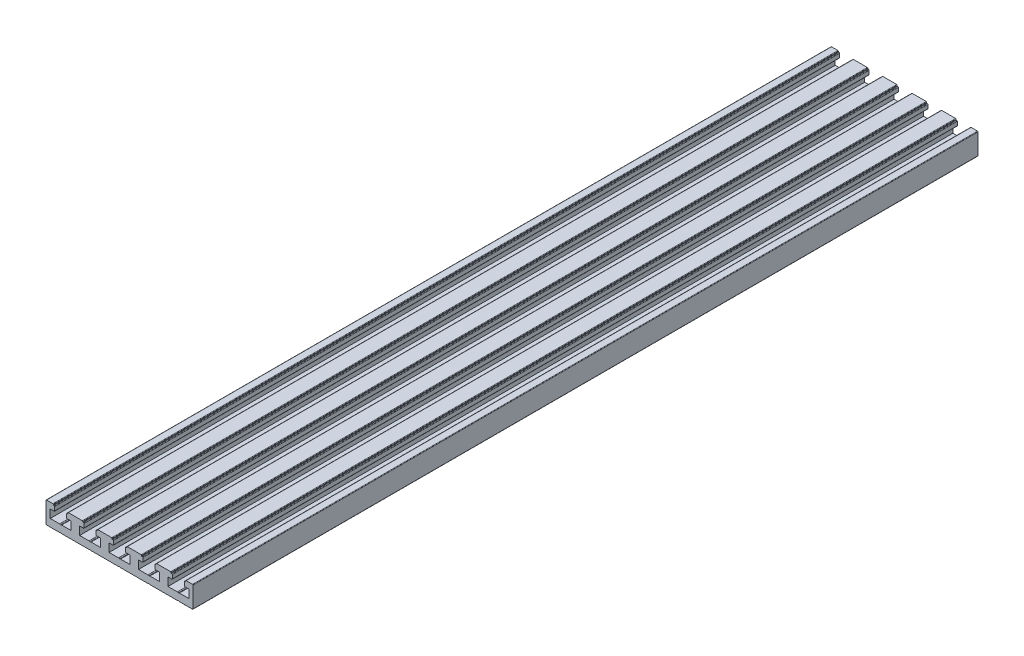
SolidWorks part; units mm, degrees
material "6061-T6 (SS)"
ref_plane "Front Plane" through (0, 0, 0) normal (0, 0, 1) x (1, 0, 0)
ref_plane "Top Plane" through (0, 0, 0) normal (0, 1, 0) x (1, 0, 0)
ref_plane "Right Plane" through (0, 0, 0) normal (1, 0, 0) x (0, 0, -1)
sketch "Sketch1" plane through (0, 0, 0) normal (0, 0, -1) x (-1, 0, 0)
  line L0 (0, 1.72) -> (0, -1.72) construction
  line L1 (-37.45, 8.85) -> (-37.45, -1.65)
  line L2 (-37.2, -1.9) -> (-30.5436, -1.9)
  line L3 (-30.4589, -1.8852) -> (-30, -1.72)
  line L4 (-30, -1.72) -> (-29.5411, -1.8852)
  line L5 (-29.4564, -1.9) -> (-15.5436, -1.9)
  line L6 (-15.4589, -1.8852) -> (-15, -1.72)
  line L7 (-15, -1.72) -> (-14.5411, -1.8852)
  line L8 (-14.4564, -1.9) -> (-0.5436, -1.9)
  line L9 (-0.4589, -1.8852) -> (0, -1.72)
  line L10 (0, -1.72) -> (0.4589, -1.8852)
  line L11 (0.5436, -1.9) -> (14.4564, -1.9)
  line L12 (14.5411, -1.8852) -> (15, -1.72)
  line L13 (15, -1.72) -> (15.4589, -1.8852)
  line L14 (15.5436, -1.9) -> (29.4564, -1.9)
  line L15 (29.5411, -1.8852) -> (30, -1.72)
  line L16 (30, -1.72) -> (30.4589, -1.8852)
  line L17 (30.5436, -1.9) -> (37.2, -1.9)
  line L18 (37.45, -1.65) -> (37.45, 8.85)
  line L19 (37.2, 9.1) -> (33.95, 9.1)
  line L20 (33.7, 8.85) -> (33.7, 8.5)
  line L21 (33.7, 8.5) -> (33.32, 8.5)
  line L22 (33.07, 8.25) -> (33.07, 6.35)
  line L23 (33.32, 6.1) -> (35.3, 6.1)
  line L24 (35.3, 6.1) -> (35.3, 1.9)
  line L25 (35.3, 1.9) -> (30.5436, 1.9)
  line L26 (30.4589, 1.8852) -> (30, 1.72)
  line L27 (30, 1.72) -> (29.5411, 1.8852)
  line L28 (29.4564, 1.9) -> (24.7, 1.9)
  line L29 (24.7, 1.9) -> (24.7, 6.1)
  line L30 (24.7, 6.1) -> (26.68, 6.1)
  line L31 (26.93, 6.35) -> (26.93, 8.25)
  line L32 (26.68, 8.5) -> (26.3, 8.5)
  line L33 (26.3, 8.5) -> (26.3, 8.85)
  line L34 (26.05, 9.1) -> (18.95, 9.1)
  line L35 (18.7, 8.85) -> (18.7, 8.5)
  line L36 (18.7, 8.5) -> (18.32, 8.5)
  line L37 (18.07, 8.25) -> (18.07, 6.35)
  line L38 (18.32, 6.1) -> (20.3, 6.1)
  line L39 (20.3, 6.1) -> (20.3, 1.9)
  line L40 (20.3, 1.9) -> (15.5436, 1.9)
  line L41 (15.4589, 1.8852) -> (15, 1.72)
  line L42 (15, 1.72) -> (14.5411, 1.8852)
  line L43 (14.4564, 1.9) -> (9.7, 1.9)
  line L44 (9.7, 1.9) -> (9.7, 6.1)
  line L45 (9.7, 6.1) -> (11.68, 6.1)
  line L46 (11.93, 6.35) -> (11.93, 8.25)
  line L47 (11.68, 8.5) -> (11.3, 8.5)
  line L48 (11.3, 8.5) -> (11.3, 8.85)
  line L49 (11.05, 9.1) -> (3.95, 9.1)
  line L50 (3.7, 8.85) -> (3.7, 8.5)
  line L51 (3.7, 8.5) -> (3.32, 8.5)
  line L52 (3.07, 8.25) -> (3.07, 6.35)
  line L53 (3.32, 6.1) -> (5.3, 6.1)
  line L54 (5.3, 6.1) -> (5.3, 1.9)
  line L55 (5.3, 1.9) -> (0.5436, 1.9)
  line L56 (0.4589, 1.8852) -> (0, 1.72)
  line L57 (0, 1.72) -> (-0.4589, 1.8852)
  line L58 (-0.5436, 1.9) -> (-5.3, 1.9)
  line L59 (-5.3, 1.9) -> (-5.3, 6.1)
  line L60 (-5.3, 6.1) -> (-3.32, 6.1)
  line L61 (-3.07, 6.35) -> (-3.07, 8.25)
  line L62 (-3.32, 8.5) -> (-3.7, 8.5)
  line L63 (-3.7, 8.5) -> (-3.7, 8.85)
  line L64 (-3.95, 9.1) -> (-11.05, 9.1)
  line L65 (-11.3, 8.85) -> (-11.3, 8.5)
  line L66 (-11.3, 8.5) -> (-11.68, 8.5)
  line L67 (-11.93, 8.25) -> (-11.93, 6.35)
  line L68 (-11.68, 6.1) -> (-9.7, 6.1)
  line L69 (-9.7, 6.1) -> (-9.7, 1.9)
  line L70 (-9.7, 1.9) -> (-14.4564, 1.9)
  line L71 (-14.5411, 1.8852) -> (-15, 1.72)
  line L72 (-15, 1.72) -> (-15.4589, 1.8852)
  line L73 (-15.5436, 1.9) -> (-20.3, 1.9)
  line L74 (-20.3, 1.9) -> (-20.3, 6.1)
  line L75 (-20.3, 6.1) -> (-18.32, 6.1)
  line L76 (-18.07, 6.35) -> (-18.07, 8.25)
  line L77 (-18.32, 8.5) -> (-18.7, 8.5)
  line L78 (-18.7, 8.5) -> (-18.7, 8.85)
  line L79 (-18.95, 9.1) -> (-26.05, 9.1)
  line L80 (-26.3, 8.85) -> (-26.3, 8.5)
  line L81 (-26.3, 8.5) -> (-26.68, 8.5)
  line L82 (-26.93, 8.25) -> (-26.93, 6.35)
  line L83 (-26.68, 6.1) -> (-24.7, 6.1)
  line L84 (-24.7, 6.1) -> (-24.7, 1.9)
  line L85 (-24.7, 1.9) -> (-29.4564, 1.9)
  line L86 (-29.5411, 1.8852) -> (-30, 1.72)
  line L87 (-30, 1.72) -> (-30.4589, 1.8852)
  line L88 (-30.5436, 1.9) -> (-35.3, 1.9)
  line L89 (-35.3, 1.9) -> (-35.3, 6.1)
  line L90 (-35.3, 6.1) -> (-33.32, 6.1)
  line L91 (-33.07, 6.35) -> (-33.07, 8.25)
  line L92 (-33.32, 8.5) -> (-33.7, 8.5)
  line L93 (-33.7, 8.5) -> (-33.7, 8.85)
  line L94 (-33.95, 9.1) -> (-37.2, 9.1)
  arc A0 (-37.45, -1.65) -> (-37.2, -1.9) centre (-37.2, -1.65) ccw
  arc A1 (-30.5436, -1.9) -> (-30.4589, -1.8852) centre (-30.5436, -1.65) ccw
  arc A2 (-29.5411, -1.8852) -> (-29.4564, -1.9) centre (-29.4564, -1.65) ccw
  arc A3 (-15.5436, -1.9) -> (-15.4589, -1.8852) centre (-15.5436, -1.65) ccw
  arc A4 (-14.5411, -1.8852) -> (-14.4564, -1.9) centre (-14.4564, -1.65) ccw
  arc A5 (-0.5436, -1.9) -> (-0.4589, -1.8852) centre (-0.5436, -1.65) ccw
  arc A6 (0.4589, -1.8852) -> (0.5436, -1.9) centre (0.5436, -1.65) ccw
  arc A7 (14.4564, -1.9) -> (14.5411, -1.8852) centre (14.4564, -1.65) ccw
  arc A8 (15.4589, -1.8852) -> (15.5436, -1.9) centre (15.5436, -1.65) ccw
  arc A9 (29.4564, -1.9) -> (29.5411, -1.8852) centre (29.4564, -1.65) ccw
  arc A10 (30.4589, -1.8852) -> (30.5436, -1.9) centre (30.5436, -1.65) ccw
  arc A11 (37.2, -1.9) -> (37.45, -1.65) centre (37.2, -1.65) ccw
  arc A12 (37.45, 8.85) -> (37.2, 9.1) centre (37.2, 8.85) ccw
  arc A13 (33.95, 9.1) -> (33.7, 8.85) centre (33.95, 8.85) ccw
  arc A14 (33.32, 8.5) -> (33.07, 8.25) centre (33.32, 8.25) ccw
  arc A15 (33.07, 6.35) -> (33.32, 6.1) centre (33.32, 6.35) ccw
  arc A16 (30.5436, 1.9) -> (30.4589, 1.8852) centre (30.5436, 1.65) ccw
  arc A17 (29.5411, 1.8852) -> (29.4564, 1.9) centre (29.4564, 1.65) ccw
  arc A18 (26.68, 6.1) -> (26.93, 6.35) centre (26.68, 6.35) ccw
  arc A19 (26.93, 8.25) -> (26.68, 8.5) centre (26.68, 8.25) ccw
  arc A20 (26.3, 8.85) -> (26.05, 9.1) centre (26.05, 8.85) ccw
  arc A21 (18.95, 9.1) -> (18.7, 8.85) centre (18.95, 8.85) ccw
  arc A22 (18.32, 8.5) -> (18.07, 8.25) centre (18.32, 8.25) ccw
  arc A23 (18.07, 6.35) -> (18.32, 6.1) centre (18.32, 6.35) ccw
  arc A24 (15.5436, 1.9) -> (15.4589, 1.8852) centre (15.5436, 1.65) ccw
  arc A25 (14.5411, 1.8852) -> (14.4564, 1.9) centre (14.4564, 1.65) ccw
  arc A26 (11.68, 6.1) -> (11.93, 6.35) centre (11.68, 6.35) ccw
  arc A27 (11.93, 8.25) -> (11.68, 8.5) centre (11.68, 8.25) ccw
  arc A28 (11.3, 8.85) -> (11.05, 9.1) centre (11.05, 8.85) ccw
  arc A29 (3.95, 9.1) -> (3.7, 8.85) centre (3.95, 8.85) ccw
  arc A30 (3.32, 8.5) -> (3.07, 8.25) centre (3.32, 8.25) ccw
  arc A31 (3.07, 6.35) -> (3.32, 6.1) centre (3.32, 6.35) ccw
  arc A32 (0.5436, 1.9) -> (0.4589, 1.8852) centre (0.5436, 1.65) ccw
  arc A33 (-0.4589, 1.8852) -> (-0.5436, 1.9) centre (-0.5436, 1.65) ccw
  arc A34 (-3.32, 6.1) -> (-3.07, 6.35) centre (-3.32, 6.35) ccw
  arc A35 (-3.07, 8.25) -> (-3.32, 8.5) centre (-3.32, 8.25) ccw
  arc A36 (-3.7, 8.85) -> (-3.95, 9.1) centre (-3.95, 8.85) ccw
  arc A37 (-11.05, 9.1) -> (-11.3, 8.85) centre (-11.05, 8.85) ccw
  arc A38 (-11.68, 8.5) -> (-11.93, 8.25) centre (-11.68, 8.25) ccw
  arc A39 (-11.93, 6.35) -> (-11.68, 6.1) centre (-11.68, 6.35) ccw
  arc A40 (-14.4564, 1.9) -> (-14.5411, 1.8852) centre (-14.4564, 1.65) ccw
  arc A41 (-15.4589, 1.8852) -> (-15.5436, 1.9) centre (-15.5436, 1.65) ccw
  arc A42 (-18.32, 6.1) -> (-18.07, 6.35) centre (-18.32, 6.35) ccw
  arc A43 (-18.07, 8.25) -> (-18.32, 8.5) centre (-18.32, 8.25) ccw
  arc A44 (-18.7, 8.85) -> (-18.95, 9.1) centre (-18.95, 8.85) ccw
  arc A45 (-26.05, 9.1) -> (-26.3, 8.85) centre (-26.05, 8.85) ccw
  arc A46 (-26.68, 8.5) -> (-26.93, 8.25) centre (-26.68, 8.25) ccw
  arc A47 (-26.93, 6.35) -> (-26.68, 6.1) centre (-26.68, 6.35) ccw
  arc A48 (-29.4564, 1.9) -> (-29.5411, 1.8852) centre (-29.4564, 1.65) ccw
  arc A49 (-30.4589, 1.8852) -> (-30.5436, 1.9) centre (-30.5436, 1.65) ccw
  arc A50 (-33.32, 6.1) -> (-33.07, 6.35) centre (-33.32, 6.35) ccw
  arc A51 (-33.07, 8.25) -> (-33.32, 8.5) centre (-33.32, 8.25) ccw
  arc A52 (-33.7, 8.85) -> (-33.95, 9.1) centre (-33.95, 8.85) ccw
  arc A53 (-37.2, 9.1) -> (-37.45, 8.85) centre (-37.2, 8.85) ccw
  point P2 (0, 0)
  dimension "D1" = 11
  dimension "D2" = 74.9
extrude "RawPart" add sketch "Sketch1" against normal blind 400
hole_wizard "CSK for M3 Flat Head Machine Screw1" positions "3DSketch1" profile "Sketch2" countersink size "M3" standard "ANSI Metric" end condition through all
sketch3d "3DSketch1"
  point P0 (-30, 1.9, 65)
  point P2 (30, 1.9, 65)
  point P35 (30, 1.9, 330)
  point P37 (-30, 1.9, 330)
  dimension "D4" = 330
  dimension "D1" = 65
  dimension "D2" = 7.45
  dimension "D3" = 60
sketch "Sketch2" plane through (-30, 1.9, 65) normal (1, 0, 0) x (0, 0, 1)
  line L0 (0, 0) -> (0, 3.8)
  line L1 (0, 3.8) -> (1.6, 3.8)
  line L2 (1.6, 3.8) -> (1.6, 1.9)
  line L3 (1.6, 1.9) -> (3, 0.5)
  line L4 (3, 0.5) -> (3, 0)
  line L6 (3, 0) -> (0, 0)
  line L7 (-1.6, 1.9) -> (-3, 0.5) construction
  line L11 (0, -6.35) -> (0, 107.95) construction
  dimension "Thru Hole Dia." = 3.2
  dimension "Thru Hole Depth" = 3.8
  dimension "C'Sink Dia." = 6
  dimension "C'Sink Angle" = 90
  dimension "Head Clearance" = 0.5
hole_wizard "M4x0.7 Tapped Hole1" positions "Sketch4" profile "Sketch5" tap size "M4x0.7" standard "ANSI Metric" end condition through all
sketch "Sketch4" plane through (0, 1.9, 0) normal (0, 1, 0) x (1, 0, 0)
  line L1 (-0.5436, 0) -> (-14.4564, 0) construction
  line L2 (-37.45, -400) -> (-37.45, 0) construction
  line L3 (15, -400) -> (15, 0) construction
  line L5 (-26.05, 0) -> (-18.95, 0) construction
  point P0 (15, -30)
  point P15 (15, -371)
  dimension "D1" = 30
  dimension "D2" = 52.45
  dimension "D3" = 371
sketch "Sketch5" plane through (15, 1.9, 30) normal (1, 0, 0) x (0, 0, 1)
  line L0 (0, 0) -> (0, 3.8)
  line L1 (0, 3.8) -> (1.65, 3.8)
  line L2 (1.65, 3.8) -> (1.65, 0)
  line L5 (1.65, 0) -> (0, 0)
  line L11 (0, -6.35) -> (0, 107.95) construction
  dimension "Thru Tap Drill Dia." = 3.3
  dimension "Thru Tap Drill Depth" = 3.8
cosmetic thread "Hole Thread4" parameters "D2"=4
cosmetic thread "Hole Thread7" parameters "D2"=4
sketch "Sketch6" [suppressed] plane through (0, 0, 0) normal (0, 0, -1) x (-1, 0, 0)
  line L1 (-14.5411, -9.9057) -> (-41.3903, -9.9057)
  line L2 (-14.5411, -9.9057) -> (-14.5411, 14.5956)
  line L3 (-14.5411, 14.5956) -> (-41.3903, 14.5956)
  line L4 (-41.3903, -9.9057) -> (-41.3903, 14.5956)
extrude "CutUnnecessaryHalf" [suppressed] cut sketch "Sketch6" against normal through all
equation "\"D4@3DSketch1\"=\"D1@RawPart\"-\"D1@3DSketch1\"-5"
